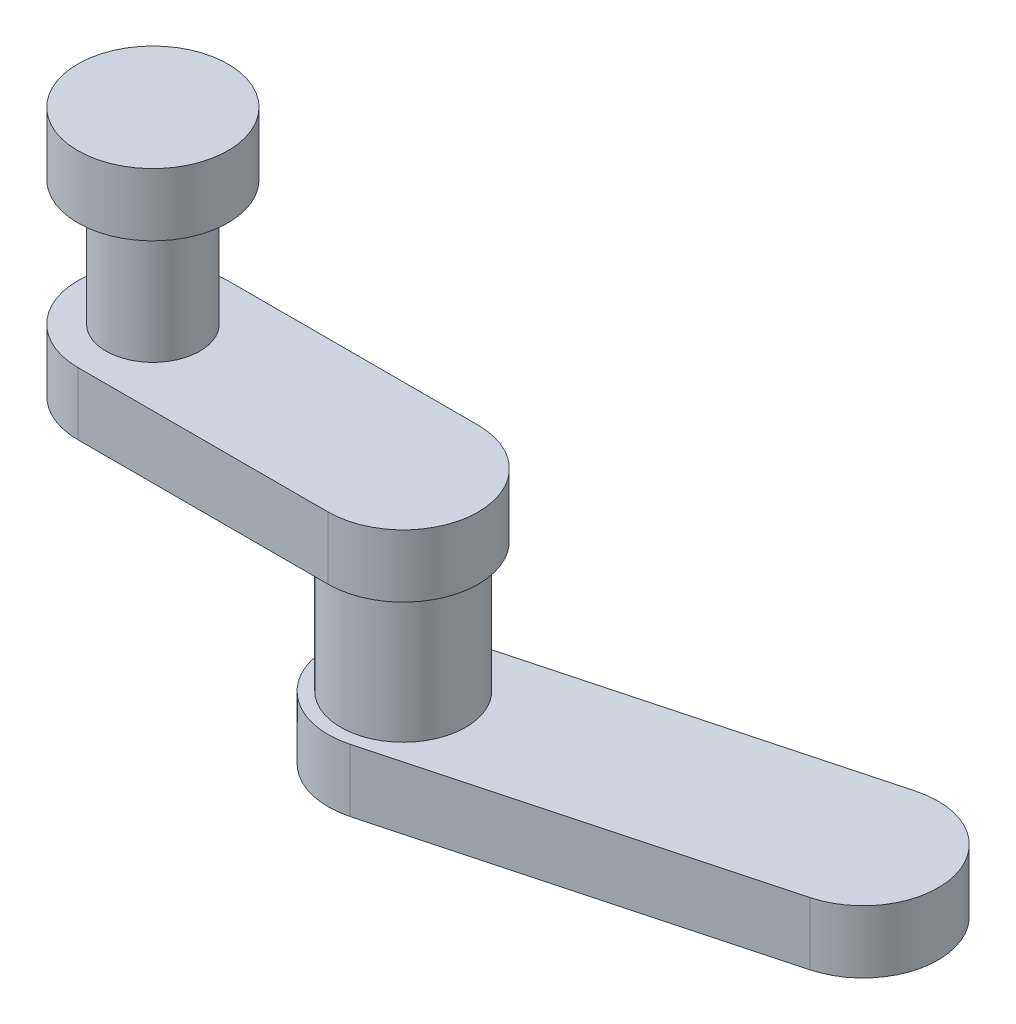
SolidWorks part; units mm, degrees
ref_plane "Front Plane" through (0, 0, 0) normal (0, 0, 1) x (1, 0, 0)
ref_plane "Top Plane" through (0, 0, 0) normal (0, 1, 0) x (1, 0, 0)
ref_plane "Right Plane" through (0, 0, 0) normal (1, 0, 0) x (0, 0, -1)
sketch "Sketch1" plane through (0, 0, 0) normal (0, 1, 0) x (1, 0, 0)
  circle A0 centre (0, 0) radius 3.175
  dimension "D1" = 6.35
extrude "Boss-Extrude1" add sketch "Sketch1" along normal blind 6.604
sketch "Sketch2" plane through (0, 6.604, 0) normal (0, 1, 0) x (1, 0, 0)
  line L0 (0, 0) -> (-12.7, 0) construction
  line L1 (0, -3.81) -> (-12.7, -3.81)
  line L2 (0, 3.81) -> (-12.7, 3.81)
  arc A0 (0, -3.81) -> (0, 3.81) centre (0, 0) ccw
  arc A1 (-12.7, 3.81) -> (-12.7, -3.81) centre (-12.7, 0) ccw
  circle A2 centre (-12.7, 0) radius 2.3813
  point P3 (-6.35, 0)
  dimension "D1" = 3.81
  dimension "D3" = 4.7625
  dimension "D2" = 12.7
extrude "Boss-Extrude2" add sketch "Sketch2" along normal blind 3.175
extrude "Boss-Extrude3" add sketch "Sketch2<3>" along normal blind 9.525 contours A2 region at (-12.7, 6.604, 0)
sketch "Sketch2<3>" plane through (0, 6.604, 0) normal (0, 1, 0) x (1, 0, 0) same geometry as "Sketch2"
sketch "Sketch4" plane through (0, 16.129, 0) normal (0, 1, 0) x (1, 0, 0)
  arc A1 (-12.7, 3.81) -> (-12.7, -3.81) centre (-12.7, 0) ccw construction
  circle A3 centre (-12.7, 0) radius 3.81
extrude "Boss-Extrude4" add sketch "Sketch4" along normal blind 3.175
sketch "Sketch5" plane through (0, 0, 0) normal (0, -1, 0) x (1, 0, 0)
  line L0 (0, 0) -> (18.4009, -4.9305) construction
  line L1 (0.9861, 3.6802) -> (19.387, -1.2503)
  line L2 (-0.9861, -3.6802) -> (17.4148, -8.6107)
  line L3 (0, 0) -> (28.6671, 0) construction
  arc A0 (0.9861, 3.6802) -> (-0.9861, -3.6802) centre (0, 0) ccw
  arc A1 (17.4148, -8.6107) -> (19.387, -1.2503) centre (18.4009, -4.9305) ccw
  arc A2 (0, -3.81) -> (0, 3.81) centre (0, 0) ccw construction
  point P3 (9.2004, -2.4653)
  dimension "D1" = 15
  dimension "D2" = 19.05
extrude "Boss-Extrude5" add sketch "Sketch5" along normal blind 3.175
